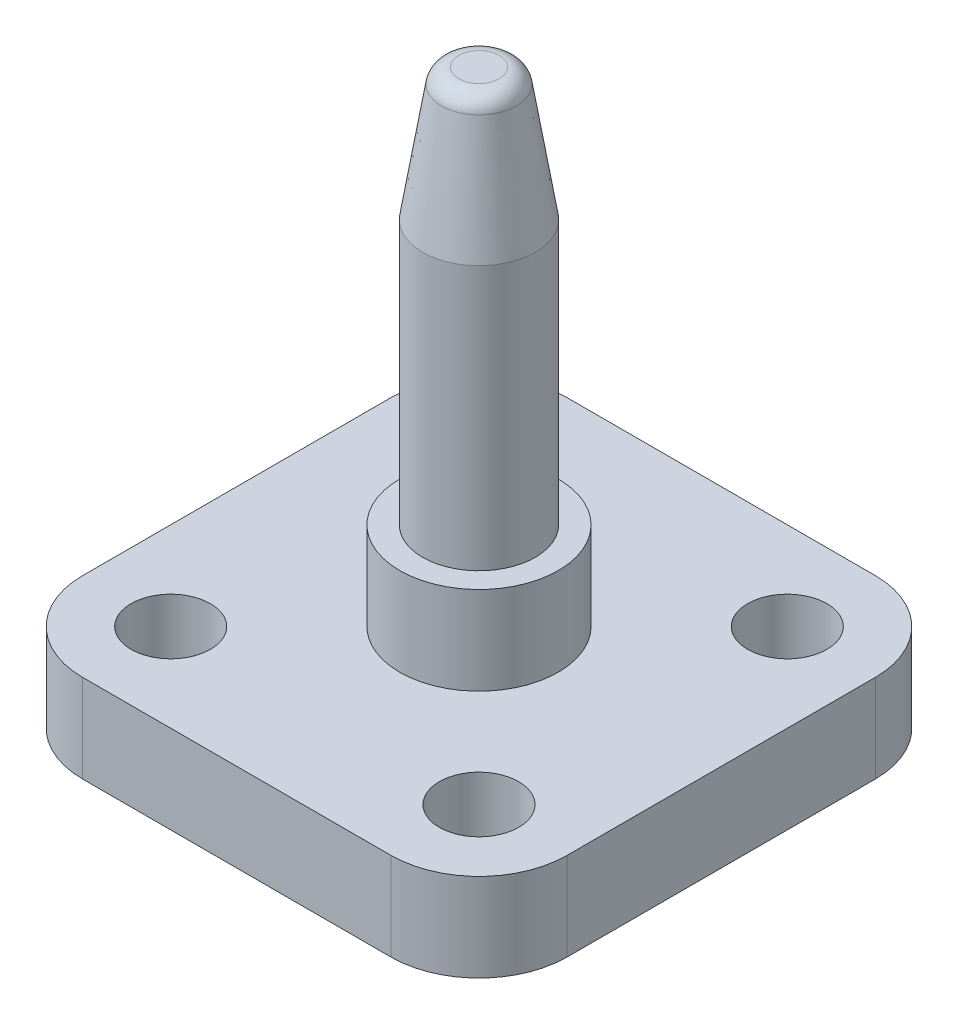
SolidWorks part; units mm, degrees
ref_plane "Front Plane" through (0, 0, 0) normal (0, 0, 1) x (1, 0, 0)
ref_plane "Top Plane" through (0, 0, 0) normal (0, 1, 0) x (1, 0, 0)
ref_plane "Right Plane" through (0, 0, 0) normal (1, 0, 0) x (0, 0, -1)
sketch "Sketch1" plane through (0, 0, 0) normal (0, 0, 1) x (1, 0, 0)
  line L0 (0, 27.5) -> (0, -27.5) construction
  line L1 (0, 27.5) -> (2.2946, 27.5)
  line L2 (4.2694, 25.816) -> (6.4, 12.5)
  line L3 (6.4, 12.5) -> (6.4, -17.5)
  line L4 (6.4, -27.5) -> (0, -27.5)
  line L5 (0, 27.5) -> (0, -27.5)
  line L6 (6.4, -17.5) -> (9, -17.5)
  line L7 (9, -17.5) -> (9, -27.5)
  line L8 (9, -27.5) -> (6.4, -27.5)
  arc A0 (2.2946, 27.5) -> (4.2694, 25.816) centre (2.2946, 25.5) cw
  point P4 (0, 0)
  point P10 (4, 27.5)
  dimension "D5" = 2
  dimension "D1" = 40
  dimension "D2" = 15
  dimension "D3" = 12.8
  dimension "D4" = 4
  dimension "D6" = 9
  dimension "D7" = 10
revolve "Revolve1" add sketch "Sketch1" angle 360 about L0
sketch "Sketch2" plane through (0, -27.5, 0) normal (0, -1, 0) x (1, 0, 0)
  line L0 (27.5, 27.5) -> (-27.5, -27.5) construction
  line L1 (17.5, 27.5) -> (-17.5, 27.5)
  line L2 (27.5, 17.5) -> (27.5, -17.5)
  line L3 (17.5, -27.5) -> (-17.5, -27.5)
  line L4 (-27.5, 17.5) -> (-27.5, -17.5)
  arc A0 (-17.5, 27.5) -> (-27.5, 17.5) centre (-17.5, 17.5) ccw
  arc A1 (-17.5, -27.5) -> (-27.5, -17.5) centre (-17.5, -17.5) cw
  arc A2 (27.5, -17.5) -> (17.5, -27.5) centre (17.5, -17.5) cw
  arc A3 (17.5, 27.5) -> (27.5, 17.5) centre (17.5, 17.5) cw
  dimension "D2" = 10
  dimension "D1" = 55
extrude "Boss-Extrude1" add sketch "Sketch2" along normal blind 10
sketch "Sketch3" plane through (0, -27.5, 0) normal (0, 1, 0) x (1, 0, 0)
  circle A0 centre (-17.5, 17.5) radius 4.5
  dimension "D1" = 9
extrude "Cut-Extrude1" cut sketch "Sketch3" against normal through all
mirror "Mirror1" about plane through (0, 0, 0) normal (0, 0, 1) of "Cut-Extrude1" second plane through (0, 0, 0) second plane normal (1, 0, 0)
